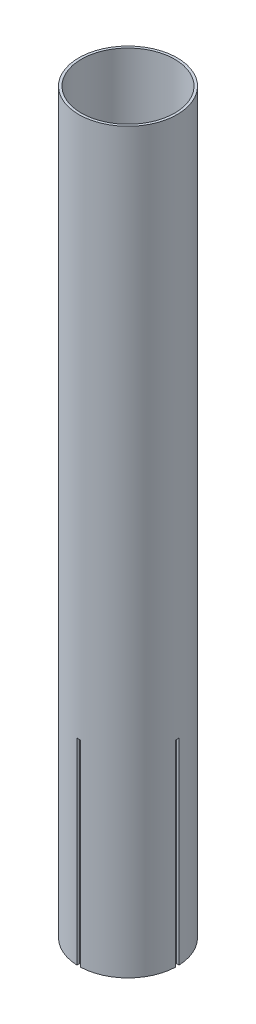
SolidWorks part; units mm, degrees
ref_plane "Front Plane" through (0, 0, 0) normal (0, 0, 1) x (1, 0, 0)
ref_plane "Top Plane" through (0, 0, 0) normal (0, 1, 0) x (1, 0, 0)
ref_plane "Right Plane" through (0, 0, 0) normal (1, 0, 0) x (0, 0, -1)
sketch "Sketch1" plane through (0, 0, 0) normal (0, 1, 0) x (1, 0, 0)
  circle A0 centre (0, 0) radius 38
  circle A1 centre (0, 0) radius 40
  dimension "D1" = 80
  dimension "D2" = 2
extrude "Boss-Extrude1" add sketch "Sketch1" along normal blind 600
sketch "Sketch2" plane through (0, 0, 0) normal (1, 0, 0) x (0, 0, -1)
  line L0 (-40, 0) -> (40, 0) construction
  line L1 (1.5, 160) -> (-1.5, 160)
  line L2 (1.5, 160) -> (1.5, 0)
  line L3 (1.5, 0) -> (-1.5, 0)
  line L4 (-1.5, 160) -> (-1.5, 0)
  line L5 (1.5, 160) -> (-1.5, 0) construction
  line L6 (1.5, 0) -> (-1.5, 160) construction
  point P0 (0, 80)
  dimension "D1" = 3
  dimension "D2" = 160
extrude "Cut-Extrude1" cut sketch "Sketch2" against normal through all
pattern_circular "CirPattern1" count 4 over 360 about axis through (0, 600, 0) along (0, -1, 0) of "Cut-Extrude1"
